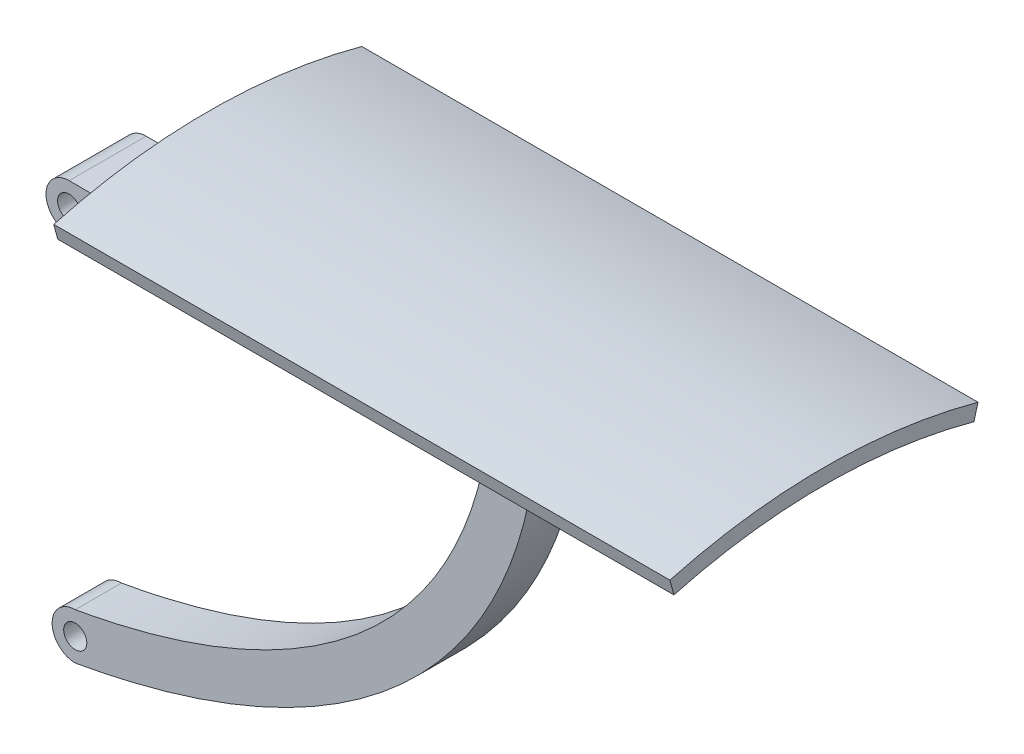
SolidWorks part; units mm, degrees
ref_plane "Plan de face" through (0, 0, 0) normal (0, 0, 1) x (1, 0, 0)
ref_plane "Plan de dessus" through (0, 0, 0) normal (0, 1, 0) x (1, 0, 0)
ref_plane "Plan de droite" through (0, 0, 0) normal (1, 0, 0) x (0, 0, -1)
sketch "Esquisse1" plane through (0, 0, 0) normal (1, 0, 0) x (0, 0, -1)
  line L0 (-20, 73.5285) -> (0, 0) construction
  line L1 (0, 0) -> (20, 73.5285) construction
  line L2 (-20, 73.5285) -> (20, 73.5285) construction
  line L3 (0, 73.5285) -> (0, 0) construction
  line L4 (-20, 73.5285) -> (-19.4751, 71.5986)
  line L5 (20, 73.5285) -> (19.4751, 71.5986)
  arc A0 (-20, 73.5285) -> (20, 73.5285) centre (0, 0) cw
  arc A1 (-19.4751, 71.5986) -> (19.4751, 71.5986) centre (0, 0) cw
  dimension "D1" = 76.2
  dimension "D2" = 30.433
  dimension "D3" = 2
  dimension "D4" = 40
extrude "Boss.-Extru.1" add sketch "Esquisse1" along normal blind 80
sketch "Esquisse7" plane through (0, 0, 0) normal (0, 0, 1) x (1, 0, 0)
  line L0 (7, 74.2) -> (7, 66.4476)
  line L1 (80, 74.2) -> (0, 74.2) construction
  line L2 (7, 74.2) -> (13, 74.2)
  line L3 (13, 74.2) -> (13, 61.6429)
  line L4 (13, 61.6429) -> (-5.1682, 58.4394)
  line L5 (-5.1682, 58.4394) -> (-13, 58.4394)
  line L6 (-13, 58.4394) -> (-13, 64.4394) construction
  line L7 (-13, 64.4394) -> (-4.3892, 64.4394)
  line L8 (-4.3892, 64.4394) -> (7, 66.4476)
  line L9 (3.9159, 60.0411) -> (1.3054, 65.4435) construction
  line L10 (10, 74.2) -> (0, 74.2) construction
  line L11 (-13, 61.4394) -> (-4.3892, 61.4394) construction
  line L12 (-4.3892, 61.4394) -> (-4.3892, 64.4394) construction
  line L13 (-4.3892, 61.4394) -> (-4.3892, 58.4394) construction
  line L14 (-4.3892, 64.4394) -> (-13.0716, 113.6797) construction
  circle A0 centre (-13, 61.4394) radius 1.5
  arc A1 (-13, 64.4394) -> (-13, 58.4394) centre (-13, 61.4394) ccw
  point P19 (-15.6854, 113.6797)
  point P21 (7, 67.4086)
  point P22 (7, 66.4476)
  dimension "D3" = 3
  dimension "D1" = 6
  dimension "D2" = 10
  dimension "D4" = 23
  dimension "D5" = 12.7606
  dimension "D6" = 80
  dimension "D7" = 50
  dimension "D8" = 170
extrude "Boss.-Extru.3" add sketch "Esquisse7" along normal blind 5 and the other way blind 5 contours L7 L8 L0 L2 L3 L4 L5 A1 | A0
sketch "Esquisse3" plane through (0, 0, 0) normal (0, 0, 1) x (1, 0, 0)
  line L0 (40, 74.2) -> (40, 69.2)
  line L1 (80, 74.2) -> (13, 74.2) construction
  line L2 (40, 69.2) -> (46, 69.2) construction
  line L3 (46, 69.2) -> (46, 74.2)
  line L4 (46, 74.2) -> (40, 74.2)
  line L5 (-77.3506, 3.4658) -> (-130.4294, -5.8934) construction
  line L6 (-76.3246, -2.3533) -> (-136.1634, -12.9045) construction
  line L7 (-14.2038, 14.6003) -> (-14.2038, 8.6003) construction
  line L8 (80, 71.5986) -> (80, 73.5285) construction
  line L9 (46, -15.4845) -> (46, -24.4681) construction
  line L10 (40, 69.2) -> (46, 69.2) construction
  line L11 (40, -127.3501) -> (40, -126.2116) construction
  line L12 (82.0482, 81.6142) -> (69.5359, 79.408) construction
  line L13 (129.6672, 36.9686) -> (87.9879, 29.6194) construction
  line L14 (123.3905, 85.4887) -> (80.4346, 77.9144) construction
  line L15 (-13, 61.4394) -> (-4.5133, 13.309) construction
  line L16 (-14.2038, 11.6003) -> (-23.2746, 63.043) construction
  arc A0 (-14.2038, 14.6003) -> (-14.2038, 8.6003) centre (-14.2038, 11.6003) ccw
  circle A1 centre (-14.2038, 11.6003) radius 1.5
  arc A2 (-14.2038, 8.6003) -> (46, 69.2) centre (-14.601, 69.2) ccw construction
  arc A3 (-14.2038, 14.6003) -> (40, 69.2) centre (-14.6012, 69.2) ccw construction
  spline S0 degree 3 poles (40, 69.2) (40, 41.395) (21.7065, 20.9322) (-14.2038, 14.6003) knots 0 0 0 0 1 1 1 1
  spline S1 degree 3 poles (46, 69.2) (46, 38.1065) (25.1934, 15.5471) (-14.2038, 8.6003) knots 0 0 0 0 1 1 1 1
  point P15 (0, 0)
  point P18 (43, 74.2)
  point P27 (-13, 61.4394)
  point P34 (0, 0)
  point P35 (0, 0)
  point P38 (0, 0)
  dimension "D4" = 3
  dimension "D5" = 37
  dimension "D1" = 49.8391
  dimension "D2" = 5
  dimension "D3" = 6
  dimension "D6" = 10
  dimension "D7" = 9.84
extrude "Boss.-Extru.2" add sketch "Esquisse3" along normal blind 3 and the other way blind 3 contours L3 L4 L0 S0 A0 S1 | A1
ref_plane "Plan2" through (0, 61.4394, 0) normal (0, 1, 0) x (1, 0, 0)
ref_plane "Plan3" through (0, 0, 0) normal (0, 0, 1) x (1, 0, 0)
